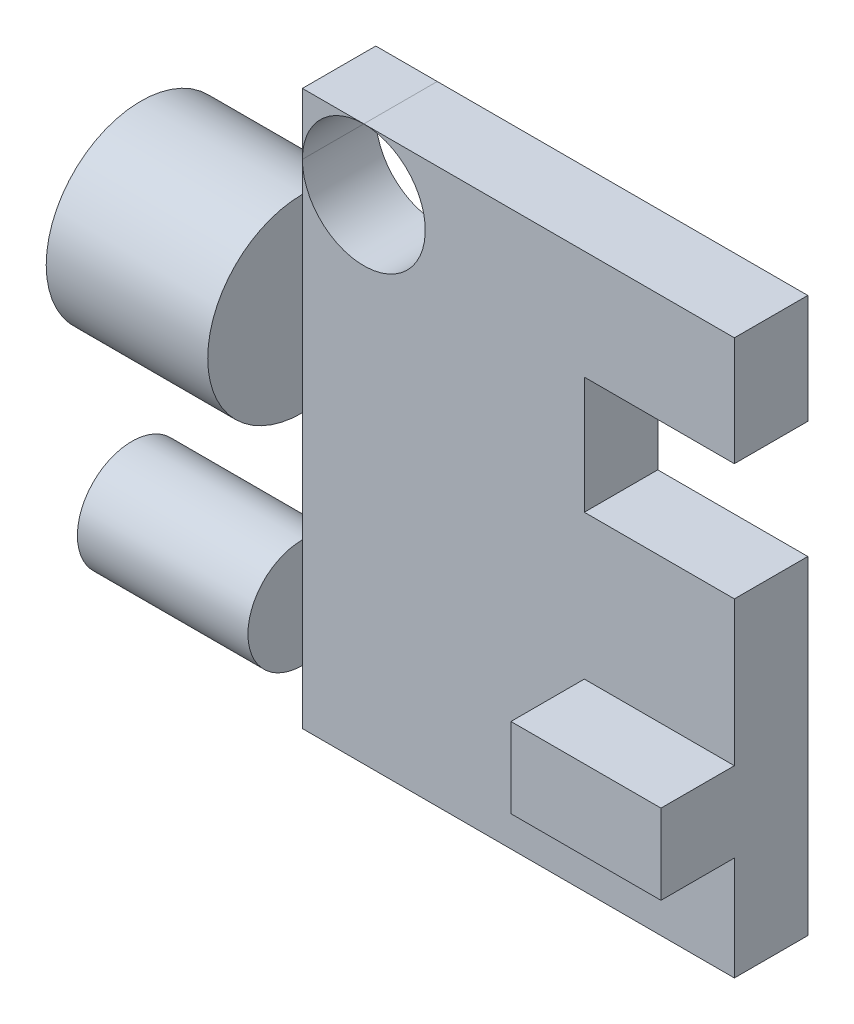
SolidWorks part; units mm, degrees
ref_plane "前视基准面" through (0, 0, 0) normal (0, 0, 1) x (1, 0, 0)
ref_plane "上视基准面" through (0, 0, 0) normal (0, 1, 0) x (1, 0, 0)
ref_plane "右视基准面" through (0, 0, 0) normal (1, 0, 0) x (0, 0, -1)
other "Configuration Table"
sketch "草图1" plane through (0, 0, 0) normal (0, 0, 1) x (1, 0, 0)
  line L0 (0, 0) -> (0, 75.5206)
  line L1 (0, 0) -> (58.8472, 0)
  line L2 (0, 75.5206) -> (58.8472, 75.5206)
  line L3 (58.8472, 75.5206) -> (58.8472, 0)
extrude "凸台-拉伸1" add sketch "草图1" along normal blind 10
sketch "草图2" plane through (0, 0, 10) normal (0, 0, 1) x (1, 0, 0)
  line L0 (0, 63.023) -> (-22.0028, 63.023)
  line L1 (0, 75.5206) -> (0, 0) construction
  line L2 (-22.0028, 63.023) -> (-22.0028, 50.1318)
  line L3 (-22.0028, 50.1318) -> (0, 50.1318)
  line L4 (0, 63.023) -> (0, 50.1318)
revolve "旋转1" add sketch "草图2" angle 360 about L3
sketch "草图3" plane through (0, 0, 10) normal (0, 0, 1) x (1, 0, 0)
  line L0 (0, 22.27) -> (-23.2318, 22.27)
  line L1 (0, 37.2405) -> (0, 0) construction
  line L2 (-23.2318, 22.27) -> (-23.2318, 14.8541)
  line L3 (-23.2318, 14.8541) -> (0, 14.8541) construction
  line L4 (0, 14.8541) -> (0, 22.27)
  line L5 (-23.2318, 14.8541) -> (0, 14.8541)
revolve "旋转2" add sketch "草图3" angle 360 about L3
sketch "草图4" plane through (0, 0, 10) normal (0, 0, 1) x (1, 0, 0)
  line L0 (58.8472, 0) -> (58.8472, 75.5206) construction
  line L1 (58.8472, 60.6666) -> (38.4093, 60.6666)
  line L2 (58.8472, 60.6666) -> (58.8472, 44.7257)
  line L3 (58.8472, 44.7257) -> (38.4093, 44.7257)
  line L4 (38.4093, 60.6666) -> (38.4093, 44.7257)
  line L6 (58.8472, 25.0423) -> (38.4093, 25.0423)
  line L7 (58.8472, 25.0423) -> (58.8472, 14.161)
  line L8 (58.8472, 14.161) -> (38.4093, 14.161)
  line L9 (38.4093, 25.0423) -> (38.4093, 14.161)
  line M6 (58.8472, 0) -> (58.8472, 75.5206)
extrude "切除-拉伸1" cut sketch "草图4" against normal blind 10 contours L1 L4 L3 M6 region at (48.6283, 52.6961, 10)
extrude "凸台-拉伸2" add sketch "草图4<3>" along normal blind 10 contours L6 L9 L8 M6 region at (48.6283, 19.6016, 10)
sketch "草图4<3>" plane through (0, 0, 10) normal (0, 0, 1) x (1, 0, 0) same geometry as "草图4"
sketch "草图5" plane through (0, 0, 10) normal (0, 0, 1) x (1, 0, 0)
  line L0 (58.8472, 75.5206) -> (0, 75.5206) construction
  line L3 (0, 75.5206) -> (0, 63.023) construction
  circle A0 centre (8.3709, 67.1497) radius 8.3709
  point P2 (17.814, 59.6157)
  point P3 (17.847, 61.2174)
  point P4 (16.8722, 62.3839)
extrude "切除-拉伸3" cut sketch "草图5" against normal blind 10
